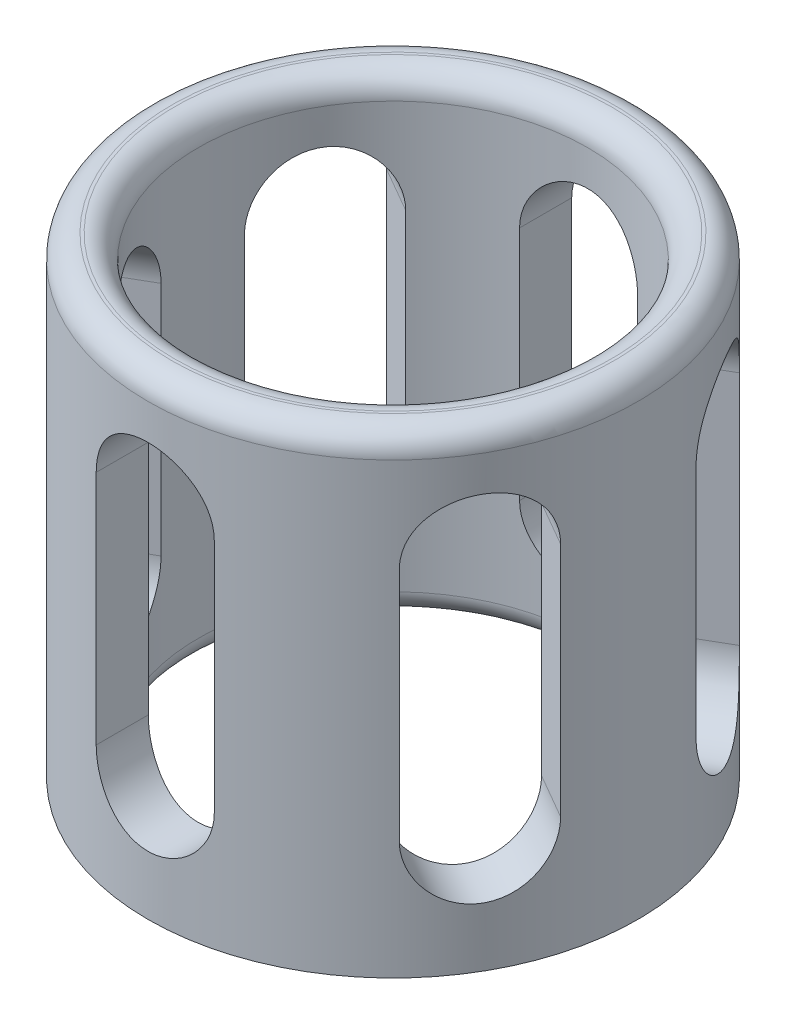
SolidWorks part; units mm, degrees
ref_plane "Front" through (0, 0, 0) normal (0, 0, 1) x (1, 0, 0)
ref_plane "Top" through (0, 0, 0) normal (0, 1, 0) x (1, 0, 0)
ref_plane "Right" through (0, 0, 0) normal (1, 0, 0) x (0, 0, -1)
sketch "Sketch1" plane through (0, 0, 0) normal (0, 1, 0) x (1, 0, 0)
  circle A0 centre (0, 0) radius 20.75
  circle A1 centre (0, 0) radius 16.5
  dimension "D1" = 41.5
  dimension "D2" = 33
extrude "Boss-Extrude1" add sketch "Sketch1" along normal blind 40
ref_plane "Plane1" through (0, 0, 20.75) normal (0, 0, 1) x (1, 0, 0)
sketch "Sketch2" plane through (0, 0, 20.75) normal (0, 0, 1) x (1, 0, 0)
  line L0 (0, 40) -> (0, 0) construction
  line L1 (20.75, 40) -> (-20.75, 40) construction
  line L2 (-20.75, 0) -> (20.75, 0) construction
  line L3 (-5, 20) -> (5, 20) construction
  line L4 (-5, 30) -> (5, 30)
  line L5 (-5, 30) -> (-5, 10)
  line L6 (-5, 10) -> (5, 10)
  line L7 (5, 30) -> (5, 10)
  line L8 (-5, 30) -> (5, 10) construction
  line L9 (-5, 10) -> (5, 30) construction
  arc A0 (-5, 30) -> (5, 30) centre (0, 30) cw
  arc A1 (-5, 10) -> (5, 10) centre (0, 10) ccw
  point P6 (0, 20)
  dimension "D1" = 10
  dimension "D2" = 20
extrude "Cut-Extrude1" cut sketch "Sketch2" against normal blind 20 contours L6 A1 | L7 L4 L5 L6 | A0 L4 region at (0, 32.1221, 20.75) region at (0, 20, 20.75) region at (0, 7.8779, 20.75)
pattern_circular "CirPattern1" count 6 over 360 about axis through (0, 40, 0) along (0, -1, 0) of "Cut-Extrude1"
fillet "Fillet1" radius 2 3 edges at (0, 40, 20.75) (0, 0, 16.5) (0, 40, 16.5)
ref_axis "Axis1" through (0, 38, 0) along (0, -1, 0)
